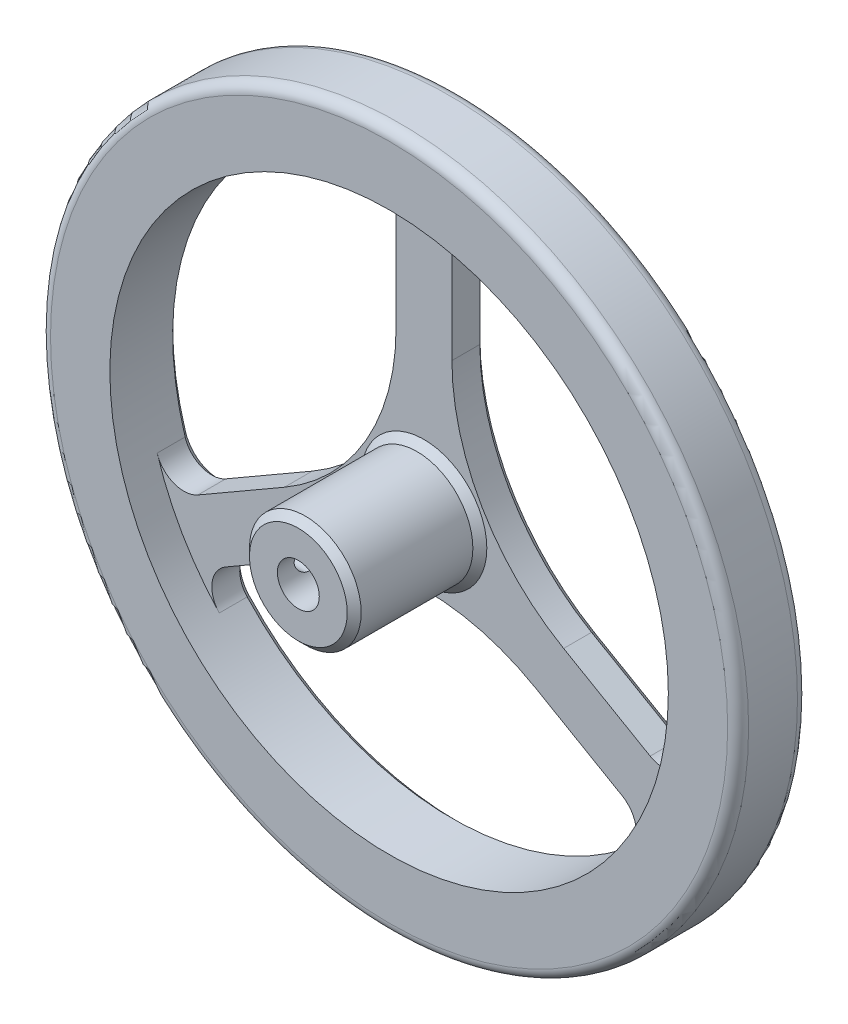
SolidWorks part; units mm, degrees
ref_plane "Front" through (0, 0, 0) normal (0, 0, 1) x (1, 0, 0)
ref_plane "Top" through (0, 0, 0) normal (0, 1, 0) x (1, 0, 0)
ref_plane "Right" through (0, 0, 0) normal (1, 0, 0) x (0, 0, -1)
sketch "Sketch1" plane through (0, 0, 0) normal (0, 0, 1) x (1, 0, 0)
  line L0 (-4, 39.7995) -> (-4, -6.9282)
  line L1 (4, 39.7995) -> (4, -6.9282)
  line L2 (36.4674, -16.4356) -> (-4, 6.9282)
  line L3 (32.4674, -23.3639) -> (-8, 0)
  line L4 (-32.4674, -23.3639) -> (8, 0)
  line L5 (-36.4674, -16.4356) -> (4, 6.9282)
  circle A0 centre (0, 0) radius 50
  circle A1 centre (0, 0) radius 40
  circle A2 centre (0, 0) radius 8
  dimension "D1" = 50
  dimension "D5" = 8
  dimension "D3" = 8
  dimension "D4" = 4
  dimension "D2" = 10
  dimension "D6" = 3
extrude "Boss-Extrude1" add sketch "Sketch1" along normal blind 10 contours A0 A1 region at (-48.5858, 0, 0)
extrude "Boss-Extrude3" add sketch "Sketch1<5>" along normal blind 5 contours L3 A2 L2 L4 L1 | A2 L3 A1 L2 | L1 A2 L0 L2 L5 | A2 L5 A1 L4 | L5 A2 L4 L0 L3 | A2 L1 A1 L0 | L0 L5 L2 | L5 L2 L1 | L5 L3 L0 | L0 L4 L3 | L1 L4 L2 | L4 L3 L1 | L5 L0 L3 L4 L1 L2 region at (0, 23.7916, 0) region at (-2.6667, 4.6188, 0) region at (0, 6.6215, 0) region at (-20.6041, -11.8958, 0) region at (0, 0, 0) region at (-5.3333, 0, 0) region at (2.6667, 4.6188, 0) region at (-5.7344, -3.3108, 0) region at (-2.6667, -4.6188, 0) region at (5.3333, 0, 0) region at (5.7344, -3.3108, 0) region at (20.6041, -11.8958, 0) region at (2.6667, -4.6188, 0)
sketch "Sketch1<5>" plane through (0, 0, 0) normal (0, 0, 1) x (1, 0, 0) same geometry as "Sketch1"
fillet "Fillet1" radius 32 3 edges at (0, -4.6188, 2.5) (-4, 2.3094, 2.5) (4, 2.3094, 2.5)
fillet "Fillet2" radius 4 6 edges at (36.4674, -16.4356, 2.5) (32.4674, -23.3639, 2.5) (-36.4674, -16.4356, 2.5) (-32.4674, -23.3639, 2.5) (-4, 39.7995, 2.5) (4, 39.7995, 2.5)
chamfer "Chamfer1" distance 1 angle 45 18 edges at (5.5056, 38.2268, 0) (8.2872, 4.7846, 0) (35.8582, -14.3454, 0) (34.641, 20, 0) (0, -9.5692, 0) (-30.3526, -23.8814, 0) (30.3526, -23.8814, 0) (0, -40, 0) (-8.2872, 4.7846, 0) (-5.5056, 38.2268, 0) (-35.8582, -14.3454, 0) (-34.641, 20, 0) (-4, 27.9422, 0) (-26.1987, -10.507, 0) (-22.1987, -17.4352, 0) (22.1987, -17.4352, 0) (26.1987, -10.507, 0) (4, 27.9422, 0)
fillet "Fillet3" radius 1.5 2 edges at (50, 0, 10) (50, 0, 0)
sketch "Sketch2" plane through (0, 0, 5) normal (0, 0, 1) x (1, 0, 0)
  circle A0 centre (0, 0) radius 8
  circle A2 centre (0, 0) radius 3
  dimension "D1" = 8
  dimension "D2" = 6
extrude "Boss-Extrude4" add sketch "Sketch2" along normal blind 18
chamfer "Chamfer2" distance 1 angle 45 2 edges at (8, 0, 23) (8, 0, 5)
sketch "Sketch3" plane through (0, 0, 0) normal (1, 0, 0) x (0, 0, -1)
  line L0 (-5, 20.7846) -> (-5, -6.9282) construction
  circle A0 centre (-19, 0) radius 1.6
  circle A1 centre (-13, 0) radius 1.6
  point P0 (-13, 0)
  point P1 (-19, 0)
  dimension "D3" = 3.2
  dimension "D1" = 8
  dimension "D2" = 6
extrude "Cut-Extrude1" cut sketch "Sketch3" against normal blind 10
equation "\"R\"= 50mm'Wheel Radius"
equation "\"T\"= 10mm'Wheel thickness"
equation "\"IT\"= 8mm'Stroke thickness"
equation "\"D1@Sketch1\"=\"R\""
equation "\"D2@Sketch1\"=\"R\"*0.2"
equation "\"D3@Sketch1\"=\"IT\""
equation "\"D4@Sketch1\"=\"IT\"/2"
equation "\"IR\"= 8mm'internal radius"
equation "\"D5@Sketch1\"=\"IR\""
equation "\"D1@Boss-Extrude1\"=\"T\""
equation "\"D1\" = \"T\" * 0.5"
equation "\"D1@Fillet1\"=\"IR\"*4"
equation "\"D1@Fillet2\"=\"IR\"*0.5"
equation "\"C\"= 1mm'Chamfer and  fillet"
equation "\"D1@Chamfer1\"=\"C\""
equation "\"D1@Fillet3\"=\"C\"*1.5"
equation "\"SR\"= 8mm'Shaft mount radius"
equation "\"D1@Sketch2\"=\"SR\""
